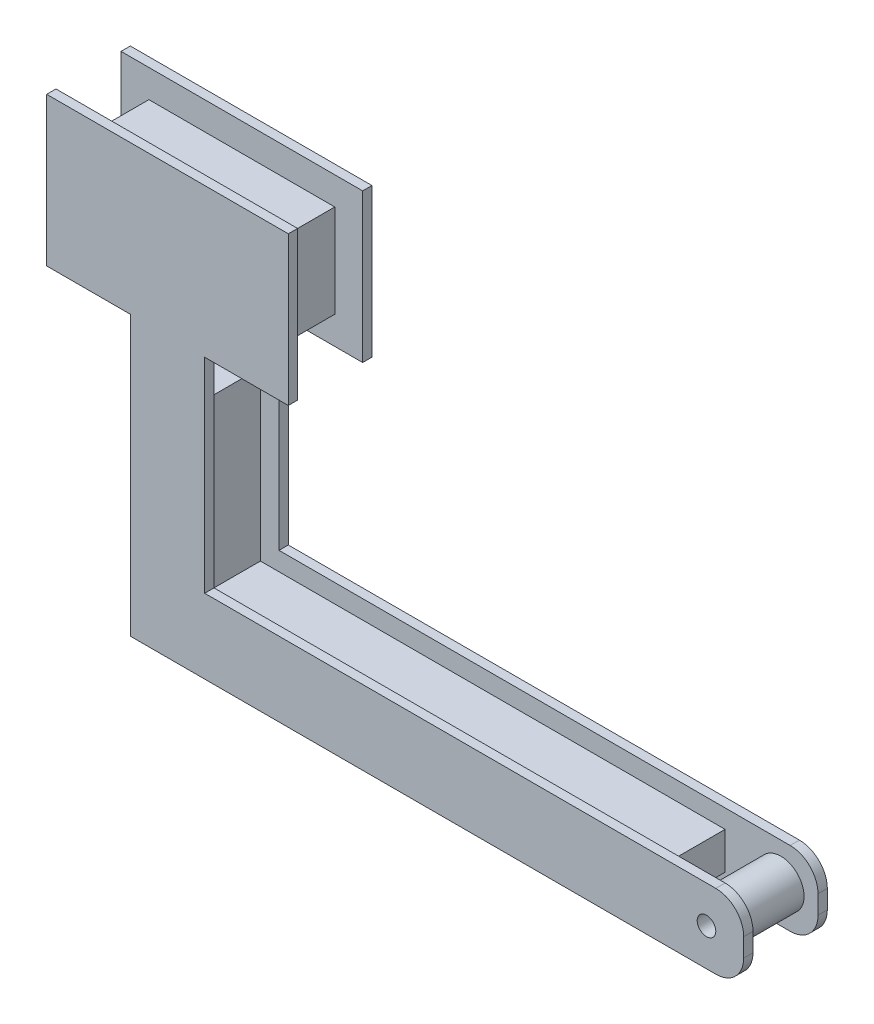
SolidWorks part; units mm, degrees
material "6061-T6 (SS)"
ref_plane "Front Plane" through (0, 0, 0) normal (0, 0, 1) x (1, 0, 0)
ref_plane "Top Plane" through (0, 0, 0) normal (0, 1, 0) x (1, 0, 0)
ref_plane "Right Plane" through (0, 0, 0) normal (1, 0, 0) x (0, 0, -1)
other "Center of Mass"
sketch "Sketch1" plane through (0, 0, 0) normal (0, 0, 1) x (1, 0, 0)
  line L1 (-50, -25) -> (50, -25)
  line L2 (-50, -25) -> (-50, 25)
  line L3 (-50, 25) -> (50, 25)
  line L4 (50, -25) -> (50, 25)
  line L5 (-50, -25) -> (50, 25) construction
  line L6 (-50, 25) -> (50, -25) construction
  point P0 (0, 0)
  dimension "D1" = 100
  dimension "D2" = 50
extrude "Boss-Extrude1" add sketch "Sketch1" along normal mid plane 35
sketch "Sketch2" plane through (0, 0, 17.5) normal (0, 0, 1) x (1, 0, 0)
  line L0 (20, -40) -> (65, -40)
  line L1 (-65, -40) -> (-20, -40)
  line L2 (-65, -40) -> (-65, 40)
  line L3 (-65, 40) -> (65, 40)
  line L4 (65, -40) -> (65, 40)
  line L5 (-65, -40) -> (65, 40) construction
  line L6 (-65, 40) -> (65, -40) construction
  line L7 (-20, -190) -> (20, -190)
  line L8 (-20, -190) -> (-20, -40)
  line L10 (20, -150) -> (20, -40)
  line L11 (-20, -190) -> (20, -40) construction
  line L12 (-20, -40) -> (20, -190) construction
  line L13 (270, -150) -> (20, -150)
  line L15 (270, -190) -> (20, -190)
  line L16 (310, -150) -> (270, -150)
  line L17 (270, -150) -> (20, -190) construction
  line L18 (270, -190) -> (20, -150) construction
  line L19 (310, -150) -> (310, -190)
  line L20 (310, -190) -> (270, -190)
  line L22 (310, -150) -> (270, -190) construction
  line L23 (310, -190) -> (270, -150) construction
  circle A0 centre (290, -170) radius 5
  point P0 (0, 0)
  point P5 (0, -115)
  point P11 (145, -170)
  point P12 (290, -170)
  dimension "D6" = 10
  dimension "D1" = 130
  dimension "D2" = 80
  dimension "D3" = 40
  dimension "D4" = 150
  dimension "D5" = 250
extrude "Boss-Extrude2" add sketch "Sketch2" along normal blind 5
mirror "Mirror1" about plane through (0, 0, 0) normal (0, 0, 1) of "Boss-Extrude2"
sketch "Sketch4" plane through (0, 0, 0) normal (0, 0, 1) x (1, 0, 0)
  line L0 (-10, -70) -> (-10, -180)
  line L1 (-10, -180) -> (260, -180)
  line L3 (260, -160) -> (10, -160)
  line L4 (10, -160) -> (10, -70)
  line L5 (-10, -70) -> (10, -70)
  line L6 (260, -160) -> (260, -180)
  line L7 (10, -160) -> (10, -40) construction
  line L8 (-10, -40) -> (-10, -180) construction
  line L10 (65, -40) -> (65, 40)
  line L11 (65, 40) -> (-65, 40)
  line L12 (-65, 40) -> (-65, -40)
  line L13 (-65, -40) -> (-20, -40)
  line L14 (-20, -40) -> (-20, -190)
  line L15 (-20, -190) -> (310, -190)
  line L16 (310, -190) -> (310, -150)
  line L17 (310, -150) -> (20, -150)
  line L18 (20, -150) -> (20, -40)
  line L19 (20, -40) -> (65, -40)
  line L20 (300, -160) -> (10, -160) construction
  line L21 (-10, -180) -> (300, -180) construction
  line L24 (-20, -40) -> (-20, -190) construction
  line L25 (-20, -190) -> (310, -190) construction
  line L26 (310, -190) -> (310, -150) construction
  line L27 (310, -150) -> (20, -150) construction
  line L28 (20, -150) -> (20, -40) construction
  line L33 (300, -180) -> (300, -160) construction
  dimension "D3" = 90
  dimension "D4" = 50
  dimension "D1" = 0
  dimension "D2" = 10
extrude "Boss-Extrude3" add sketch "Sketch4" along normal mid plane 35 contours L4 L5 L0 L1 L6 L3
fillet "Fillet1" radius 15 4 edges at (310, -190, -20) (310, -190, 20) (310, -150, -20) (310, -150, 20)
sketch "Sketch5" plane through (0, 0, 0) normal (0, 0, 1) x (1, 0, 0)
  circle A0 centre (290, -170) radius 5
  circle A1 centre (290, -170) radius 12.5
  circle A2 centre (290, -170) radius 5 construction
  dimension "D1" = 25
extrude "Boss-Extrude4" add sketch "Sketch5" along normal mid plane 35
ref_axis "Axis1" through (290, -170, 22.5) along (0, 0, -1)
ref_point "Point1"
ref_point "Point2"
